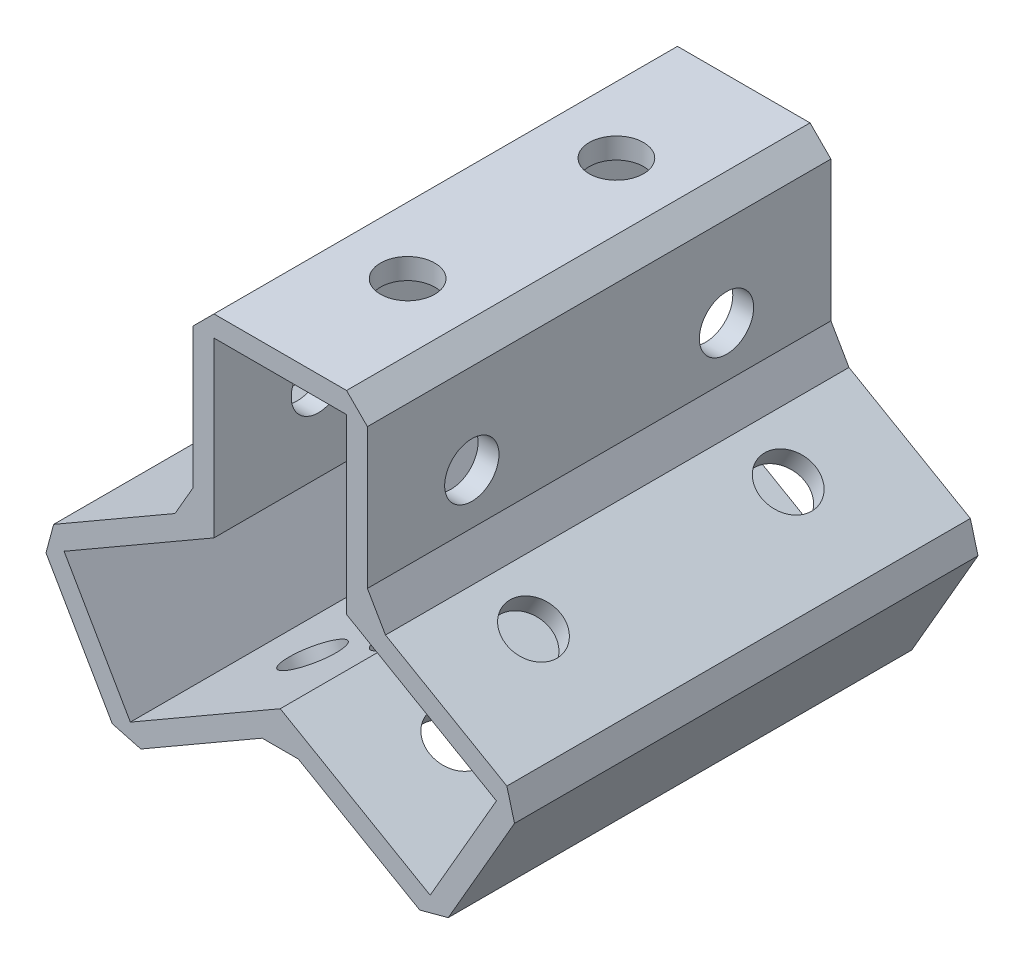
SolidWorks part; units mm, degrees
ref_plane "Front Plane" through (0, 0, 0) normal (0, 0, 1) x (1, 0, 0)
ref_plane "Top Plane" through (0, 0, 0) normal (0, 1, 0) x (1, 0, 0)
ref_plane "Right Plane" through (0, 0, 0) normal (1, 0, 0) x (0, 0, -1)
sketch "Sketch1" plane through (0, 0, 0) normal (0, 0, 1) x (1, 0, 0)
  line L0 (0, 0) -> (0, 6.3532) construction
  line L2 (-6.35, 3.6662) -> (-6.35, 20.2462)
  line L3 (-6.35, 20.2462) -> (6.35, 20.2462)
  line L4 (6.35, 3.6662) -> (6.35, 20.2462)
  line L5 (0, 0) -> (-1.6441, 0.9492) construction
  line L6 (0, 0) -> (-5.4993, -3.175) construction
  line L7 (0, 6.3532) -> (6.35, 6.3532) construction
  line L8 (-1.6441, 0.9492) -> (-4.8191, -4.55) construction
  line L9 (-5.4993, -3.175) -> (-8.6743, 2.3243) construction
  line L10 (-20.7087, -4.6238) -> (-6.35, 3.6662)
  line L11 (-20.7087, -4.6238) -> (-14.3587, -15.6223)
  line L12 (-14.3587, -15.6223) -> (0, -7.3323)
  line L13 (14.3587, -15.6223) -> (20.7087, -4.6238)
  line L14 (0, -7.3323) -> (14.3587, -15.6223)
  line L15 (20.7087, -4.6238) -> (6.35, 3.6662)
  line L16 (-8.35, 4.8209) -> (-8.35, 22.2462)
  line L17 (-8.35, 22.2462) -> (8.35, 22.2462)
  line L18 (8.35, 4.8209) -> (8.35, 22.2462)
  line L19 (23.4408, -3.8918) -> (8.35, 4.8209)
  line L20 (15.0908, -18.3544) -> (23.4408, -3.8918)
  line L21 (0, -9.6417) -> (15.0908, -18.3544)
  line L22 (-15.0908, -18.3544) -> (0, -9.6417)
  line L23 (-23.4408, -3.8918) -> (-15.0908, -18.3544)
  line L24 (-23.4408, -3.8918) -> (-8.35, 4.8209)
  line L25 (-10.5077, 0.111) -> (-5.1577, -9.1555)
  line L26 (0.2127, -7.2095) -> (-0.2873, -6.3435) construction
  line L27 (-5.6373, 2.923) -> (-19.8815, -5.3009)
  line L28 (-0.2873, -6.3435) -> (-14.5315, -14.5674)
  line L29 (-5.6373, 2.923) -> (0, 0) construction
  line L30 (0, 0) -> (-0.2873, -6.3435) construction
  line L31 (-19.8815, -5.3009) -> (-20.1688, -11.6444) construction
  line L32 (-20.1688, -11.6444) -> (-14.5315, -14.5674) construction
  line L33 (-12.7594, -1.189) -> (-7.4094, -10.4555) construction
  line L34 (-12.7594, -1.189) -> (-8.7983, 1.098)
  line L36 (-12.7594, -1.189) -> (-14.2594, 1.4091) construction
  line L37 (-5.35, 3.4205) -> (-5.35, 19.8684)
  line L38 (5.35, 3.4205) -> (5.35, 19.8684)
  line L39 (5.35, 11.6444) -> (-5.35, 11.6444) construction
  line L40 (5.35, 11.6444) -> (8.35, 11.6444) construction
  line L41 (3.35, 9.0444) -> (-5.35, 9.0444)
  line L42 (5.6373, 2.923) -> (19.8815, -5.3009)
  line L43 (0.2873, -6.3435) -> (14.5315, -14.5674)
  line L44 (7.4094, -10.4555) -> (12.7594, -1.189) construction
  line L45 (7.4094, -10.4555) -> (5.9094, -13.0535) construction
  line L46 (6.1577, -7.4234) -> (10.5077, 0.111)
  line L47 (7.4094, -10.4555) -> (5.9094, -13.0535) construction
  arc A0 (-5.6373, 2.923) -> (-0.2873, -6.3435) centre (0, 0) ccw construction
  arc A2 (-5.6373, 2.923) -> (-0.2873, -6.3435) centre (0, 0) ccw
  circle A3 centre (0, 0) radius 6.35 construction
  arc A4 (-14.5315, -14.5674) -> (-19.8815, -5.3009) centre (-20.1688, -11.6444) ccw
  arc A5 (-5.35, 19.8684) -> (5.35, 19.8684) centre (0, 23.2889) ccw
  arc A6 (5.35, 3.4205) -> (-5.35, 3.4205) centre (0, 0) ccw
  arc A7 (19.8815, -5.3009) -> (14.5315, -14.5674) centre (20.1688, -11.6444) ccw
  arc A8 (0.2873, -6.3435) -> (5.6373, 2.923) centre (0, 0) ccw
  point P64 (0, 0)
  dimension "D1" = 2
  dimension "D19" = 12.7
  dimension "D2" = 120
  dimension "D3" = 120
  dimension "D4" = 120
  dimension "D5" = 6.35
  dimension "D6" = 6.35
  dimension "D7" = 6.35
  dimension "D8" = 12.7
  dimension "D9" = 16.58
  dimension "D10" = 16.58
  dimension "D11" = 16.58
  dimension "D12" = 16.58
  dimension "D13" = 16.58
  dimension "D14" = 16.58
  dimension "D15" = 1
  dimension "D16" = 1
  dimension "D17" = 2.6
  dimension "D20" = 3
extrude "Boss-Extrude1" add sketch "Sketch1" along normal blind 44.4 contours L24 L23 L22 L21 L20 L19 L18 L17 L16 L15 L13 L14 L12 L11 L10 L2 L3 L4 region at (-7.7298, 13.5335, 0)
sketch "Sketch4" plane through (-4.175, 7.2313, 0) normal (-0.5, 0.866, 0) x (0.866, 0.5, 0)
  line L0 (-11.6444, 0) -> (-11.6444, -44.4) construction
  line L2 (-22.2462, -44.4) -> (-4.8209, -44.4) construction
  circle A0 centre (-11.6444, -10) radius 2.6
  circle A1 centre (-11.6444, -34.4) radius 2.6
  dimension "D1" = 5.2
  dimension "D2" = 10
  dimension "D3" = 5.2
  dimension "D4" = 10
extrude "Cut-Extrude1" cut sketch "Sketch4" against normal through all
sketch "Sketch5" plane through (0, 0, 0) normal (0, 1, 0) x (1, 0, 0)
  line L0 (0, 0) -> (0, -44.4) construction
sketch "Sketch6" plane through (0, 22.2462, 0) normal (0, 1, 0) x (1, 0, 0)
  line L0 (0, -22.2) -> (0, -12.2) construction
  line L1 (0, 200000) -> (0, -200044.4) construction
  line L2 (0, -22.2) -> (0, -32.2) construction
  circle A0 centre (0, -12.2) radius 2.6
  circle A1 centre (0, -32.2) radius 2.6
  dimension "D2" = 5.2
  dimension "D4" = 5.2
  dimension "D1" = 10
  dimension "D3" = 10
extrude "Cut-Extrude2" cut sketch "Sketch6" against normal through all
chamfer "Chamfer1" distance 2 distance2 2 11 edges at (-8.35, 4.8209, 22.2) (-8.35, 22.2462, 22.2) (8.35, 22.2462, 22.2) (8.35, 4.8209, 22.2) (23.4408, -3.8918, 22.2) (0, -9.6417, 4.8) (0, -9.6417, 22.2) (15.0908, -18.3544, 22.2) (0, -9.6417, 39.6) (-23.4408, -3.8918, 22.2) (-15.0908, -18.3544, 22.2) tangent propagation no
sketch "Sketch7" plane through (8.35, 0, 0) normal (1, 0, 0) x (0, 0, -1)
  line L0 (0, 11.6444) -> (-44.4, 11.6444) construction
  line L1 (-44.4, 6.8209) -> (-44.4, 20.2462) construction
  circle A0 centre (-10, 11.6444) radius 2.6
  circle A1 centre (-34.4, 11.6444) radius 2.6
  dimension "D1" = 5.2
  dimension "D3" = 5.2
  dimension "D2" = 10
  dimension "D4" = 10
extrude "Cut-Extrude3" cut sketch "Sketch7" against normal through all
sketch "Sketch9" plane through (-4.175, -7.2313, 0) normal (-0.5, -0.866, 0) x (0.866, -0.5, 0)
  line L0 (11.6444, 0) -> (11.6444, 44.4) construction
  line L1 (6.8209, 44.4) -> (20.2462, 44.4) construction
  circle A0 centre (11.6444, 34.4) radius 2.6
  circle A1 centre (11.6444, 10) radius 2.6
  dimension "D1" = 5.2
  dimension "D3" = 5.2
  dimension "D2" = 10
  dimension "D4" = 10
extrude "Cut-Extrude4" cut sketch "Sketch9" against normal through all
